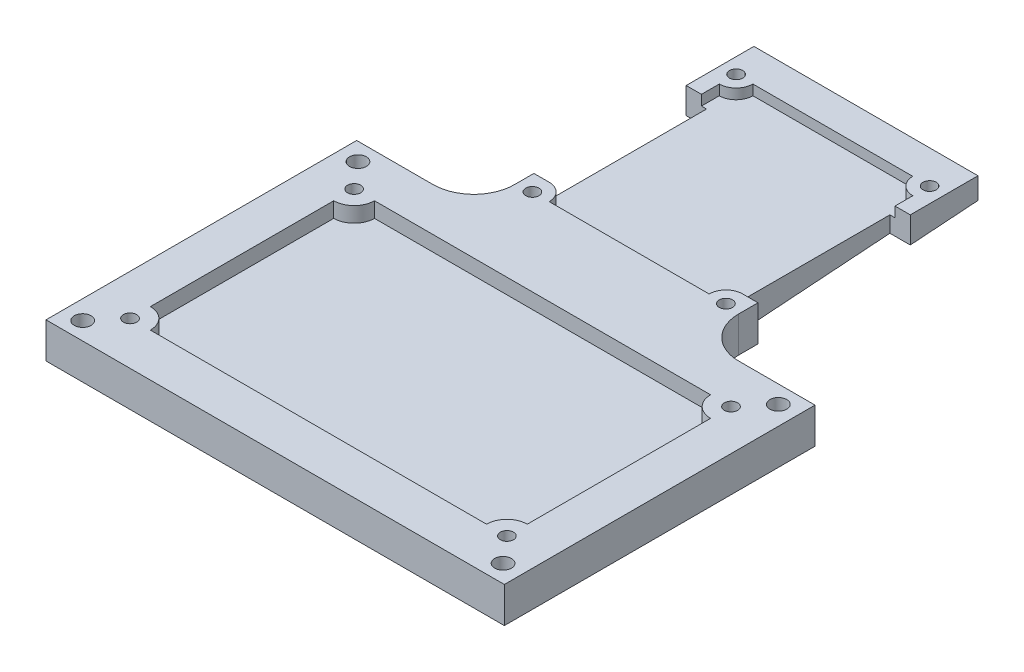
SolidWorks part; units mm, degrees
ref_plane "Front Plane" through (0, 0, 0) normal (0, 0, 1) x (1, 0, 0)
ref_plane "Top Plane" through (0, 0, 0) normal (0, 1, 0) x (1, 0, 0)
ref_plane "Right Plane" through (0, 0, 0) normal (1, 0, 0) x (0, 0, -1)
sketch "Sketch1" plane through (0, 0, 0) normal (0, 1, 0) x (1, 0, 0)
  line L0 (0, 0) -> (90, 0)
  line L1 (90, 0) -> (90, 61)
  line L2 (90, 61) -> (75, 61)
  line L3 (0, 61) -> (0, 0)
  line L4 (86.275, 3.475) -> (86.275, 57.525) construction
  line L5 (86.275, 57.525) -> (3.725, 57.525) construction
  line L6 (15, 61) -> (0, 61)
  line L8 (23, 69) -> (23, 116)
  line L9 (23, 116) -> (67, 116)
  line L10 (67, 69) -> (67, 116)
  line L11 (0, 30.5) -> (90, 30.5) construction
  circle A0 centre (3.725, 57.525) radius 1.65
  circle A1 centre (86.275, 57.525) radius 1.65
  circle A2 centre (86.275, 3.475) radius 1.65
  circle A3 centre (3.725, 3.475) radius 1.65
  arc A4 (15, 61) -> (23, 69) centre (15, 69) ccw
  arc A5 (75, 61) -> (67, 69) centre (75, 69) cw
  point P12 (86.275, 30.5)
  point P13 (90, 30.5)
  point P14 (45, 57.525)
  point P21 (45, 116)
  point P23 (23, 61)
  point P26 (45, 0)
  dimension "D5" = 3.3
  dimension "D6" = 3.3
  dimension "D7" = 3.3
  dimension "D8" = 44
  dimension "D10" = 8
  dimension "D11" = 8
  dimension "D1" = 61
  dimension "D2" = 90
  dimension "D3" = 82.55
  dimension "D4" = 54.05
  dimension "D9" = 55
extrude "Boss-Extrude1" add sketch "Sketch1" along normal blind 7
chamfer "Chamfer1" distance 40 angle 4 1 edges at (45, 0, -116) first distance on face at (86.275, 0, -1.825)
sketch "Sketch2" plane through (0, 7, 0) normal (0, 1, 0) x (1, 0, 0)
  line L0 (0, 0) -> (90, 0) construction
  line L1 (8, 52.5) -> (82, 52.5) construction
  line L2 (8, 52.5) -> (8, 8.5) construction
  line L3 (8, 8.5) -> (82, 8.5) construction
  line L4 (82, 52.5) -> (82, 8.5) construction
  line L5 (0, 61) -> (0, 0) construction
  circle A0 centre (8, 52.5) radius 1.3
  circle A1 centre (8, 8.5) radius 1.3
  circle A2 centre (82, 52.5) radius 1.3
  circle A3 centre (82, 8.5) radius 1.3
  point P10 (45, 0)
  point P11 (45, 8.5)
  point P14 (0, 30.5)
  point P15 (8, 30.5)
  dimension "D3" = 2.6
  dimension "D4" = 2.6
  dimension "D5" = 2.6
  dimension "D6" = 2.6
  dimension "D1" = 74
  dimension "D2" = 44
extrude "Cut-Extrude1" cut sketch "Sketch2" against normal through all
sketch "Sketch3" plane through (0, 7, 0) normal (0, 1, 0) x (1, 0, 0)
  line L0 (67, 116) -> (23, 116) construction
  line L1 (26, 109.5) -> (64, 109.5) construction
  line L2 (26, 109.5) -> (26, 69.5) construction
  line L3 (26, 69.5) -> (64, 69.5) construction
  line L4 (64, 109.5) -> (64, 69.5) construction
  line L5 (23, 116) -> (23, 69) construction
  circle A0 centre (26, 109.5) radius 1.3
  circle A1 centre (64, 109.5) radius 1.3
  circle A2 centre (26, 69.5) radius 1.3
  circle A3 centre (64, 69.5) radius 1.3
  dimension "D3" = 6.5
  dimension "D1" = 40
  dimension "D2" = 38
  dimension "D4" = 3
extrude "Cut-Extrude2" cut sketch "Sketch3" against normal through all
sketch "Sketch4" plane through (0, 7, 0) normal (0, 1, 0) x (1, 0, 0)
  line L1 (12, 52.5) -> (78, 52.5)
  line L2 (8, 48.5) -> (8, 12.5)
  line L3 (12, 8.5) -> (78, 8.5)
  line L4 (82, 48.5) -> (82, 12.5)
  arc A0 (8, 48.5) -> (12, 52.5) centre (8, 52.5) ccw
  arc A1 (78, 52.5) -> (82, 48.5) centre (82, 52.5) ccw
  arc A2 (82, 12.5) -> (78, 8.5) centre (82, 8.5) ccw
  arc A3 (12, 8.5) -> (8, 12.5) centre (8, 8.5) ccw
extrude "Cut-Extrude3" cut sketch "Sketch4" against normal blind 3
sketch "Sketch5" plane through (0, 7, 0) normal (0, 1, 0) x (1, 0, 0)
  line L0 (29.3, 109.5) -> (60.7, 109.5)
  line L5 (45, 106) -> (45, 71.9475) construction
  line L6 (20.5, 89.5) -> (57.0983, 89.5) construction
  line L7 (26, 106.2) -> (26, 72.8)
  line L8 (64, 106.2) -> (64, 72.8)
  line L9 (29.3, 69.5) -> (60.7, 69.5)
  circle A4 centre (26, 109.5) radius 1.3 construction
  arc A5 (26, 106.2) -> (29.3, 109.5) centre (26, 109.5) ccw
  circle A6 centre (26, 69.5) radius 1.3 construction
  circle A7 centre (64, 109.5) radius 1.3 construction
  arc A8 (26, 72.8) -> (29.3, 69.5) centre (26, 69.5) cw
  arc A9 (60.7, 69.5) -> (64, 72.8) centre (64, 69.5) cw
  arc A10 (64, 106.2) -> (60.7, 109.5) centre (64, 109.5) cw
  point P24 (26, 89.5)
  point P25 (45, 109.5)
  dimension "D1" = 3.3
  dimension "D2" = 3.3
  dimension "D3" = 3.3
  dimension "D4" = 3.3
extrude "Cut-Extrude4" cut sketch "Sketch5" against normal blind 2
sketch "Sketch6" plane through (0, 7, 0) normal (0, 1, 0) x (1, 0, 0)
  line L0 (23, 116) -> (23, 69) construction
  line L1 (27, 102.7) -> (23, 102.7)
  line L2 (27, 102.7) -> (27, 72.8)
  line L3 (27, 72.8) -> (23, 72.8)
  line L4 (23, 102.7) -> (23, 72.8)
  line L5 (45, 109.5) -> (45, 69.5) construction
  line L6 (60.7, 109.5) -> (29.3, 109.5) construction
  line L7 (29.3, 69.5) -> (60.7, 69.5) construction
  line L8 (63, 72.8) -> (67, 72.8)
  line L9 (67, 102.7) -> (67, 72.8)
  line L10 (63, 102.7) -> (67, 102.7)
  line L11 (63, 102.7) -> (63, 72.8)
  dimension "D1" = 4
extrude "Cut-Extrude5" cut sketch "Sketch6" against normal through all
sketch "Sketch7" plane through (0, 7, 0) normal (0, 1, 0) x (1, 0, 0)
  line L0 (67, 102.7) -> (67, 116) construction
  line L1 (23, 115.5) -> (67, 115.5)
  line L2 (23, 115.5) -> (23, 63.5)
  line L3 (23, 63.5) -> (67, 63.5)
  line L4 (67, 115.5) -> (67, 63.5)
  circle A1 centre (64, 109.5) radius 1.3 construction
  circle A2 centre (64, 69.5) radius 1.3 construction
  circle A3 centre (26, 109.5) radius 2
  circle A5 centre (64, 109.5) radius 2
  circle A6 centre (64, 69.5) radius 2
  circle A7 centre (26, 69.5) radius 2
  dimension "D2" = 6
  dimension "D1" = 6
extrude "Boss-Extrude2" [suppressed] add sketch "Sketch7" along normal blind 15
sketch "Sketch8" [suppressed] plane through (67, 0, 0) normal (1, 0, 0) x (0, 0, -1)
  line L0 (63.5, 22) -> (115.5, 22) construction
  line L1 (65.5, 7) -> (113.5, 7)
  line L2 (65.5, 7) -> (65.5, 19)
  line L3 (65.5, 19) -> (113.5, 19)
  line L4 (113.5, 7) -> (113.5, 19)
  line L5 (63.5, 22) -> (63.5, 7) construction
  line L6 (115.5, 22) -> (115.5, 7) construction
  dimension "D1" = 3
  dimension "D2" = 2
  dimension "D3" = 2
extrude "Cut-Extrude6" [suppressed] cut sketch "Sketch8" against normal through all
sketch "Sketch9" [suppressed] plane through (0, 0, -115.5) normal (0, 0, -1) x (-1, 0, 0)
  line L1 (-65, 7) -> (-25, 7)
  line L2 (-65, 7) -> (-65, 19)
  line L3 (-65, 19) -> (-25, 19)
  line L4 (-25, 7) -> (-25, 19)
  line L5 (-67, 22) -> (-67, 7) construction
  line L6 (-23, 22) -> (-23, 7) construction
  line L7 (-67, 22) -> (-23, 22) construction
  dimension "D1" = 2
  dimension "D2" = 2
  dimension "D3" = 3
extrude "Cut-Extrude7" [suppressed] cut sketch "Sketch9" against normal through all
equation "\"D4@Sketch2\"=\"D3@Sketch2\""
equation "\"D5@Sketch2\"=\"D3@Sketch2\""
equation "\"D6@Sketch2\"=\"D3@Sketch2\""
